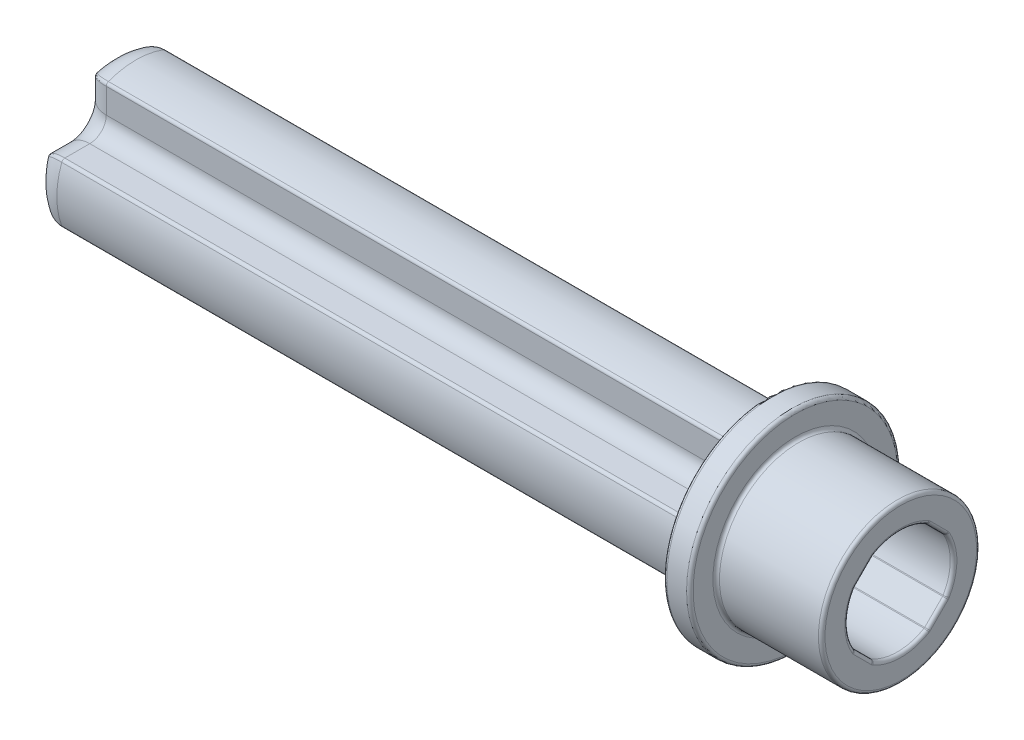
SolidWorks part; units mm, degrees
material "PET"
ref_plane "Alzado" through (0, 0, 0) normal (0, 0, 1) x (1, 0, 0)
ref_plane "Planta" through (0, 0, 0) normal (0, 1, 0) x (1, 0, 0)
ref_plane "Vista lateral" through (0, 0, 0) normal (1, 0, 0) x (0, 0, -1)
sketch "Croquis1" plane through (0, 0, 0) normal (1, 0, 0) x (0, 0, -1)
  line B0 (-1.4, 0.9) -> (-2.2249, 0.9)
  line B1 (0.9, -2.2249) -> (0.9, -1.4)
  line B2 (-0.9, -2.2249) -> (-0.9, -1.4)
  line B3 (2.2249, 0.9) -> (1.4, 0.9)
  line B4 (2.2249, -0.9) -> (1.4, -0.9)
  line B5 (-0.9, 1.4) -> (-0.9, 2.2249)
  line B6 (0.9, 1.4) -> (0.9, 2.2249)
  line B7 (-1.4, -0.9) -> (-2.2249, -0.9)
  arc B8 (-2.2249, 0.9) -> (-2.2249, -0.9) centre (0, 0) ccw
  arc B9 (-1.4, -0.9) -> (-0.9, -1.4) centre (-1.4, -1.4) cw
  arc B10 (0.9, -1.4) -> (1.4, -0.9) centre (1.4, -1.4) cw
  arc B11 (1.4, 0.9) -> (0.9, 1.4) centre (1.4, 1.4) cw
  arc B12 (-0.9, 1.4) -> (-1.4, 0.9) centre (-1.4, 1.4) cw
  arc B13 (0.9, 2.2249) -> (-0.9, 2.2249) centre (0, 0) ccw
  arc B14 (2.2249, -0.9) -> (2.2249, 0.9) centre (0, 0) ccw
  arc B15 (-0.9, -2.2249) -> (0.9, -2.2249) centre (0, 0) ccw
sketch_block_instance "Axle Section Block-1"
sketch_block "Axle Section Block" parameters "D1"=4.8, "D3"=0.5, "D2"=1.8
extrude "Saliente-Extruir1" add sketch "Croquis1" along normal blind 24
sketch "Croquis2" plane through (24, 0, 0) normal (1, 0, 0) x (0, 0, -1)
  circle A0 centre (0, 0) radius 3.2
  dimension "D1" = 6.4
extrude "Saliente-Extruir2" add sketch "Croquis2" against normal blind 4
sketch "Croquis3" plane through (24, 0, 0) normal (1, 0, 0) x (0, 0, -1)
  line L0 (-0.8154, -1.3766) -> (-1.3766, -0.8154)
  line L1 (0.8154, -1.3766) -> (1.3766, -0.8154)
  line L2 (-1.3766, 0.8154) -> (-0.8154, 1.3766)
  line L3 (1.3766, 0.8154) -> (0.8154, 1.3766)
  line L4 (2.192, 0) -> (0, 2.192) construction
  line L5 (2.192, 0) -> (0, -2.192) construction
  line L6 (0, 2.192) -> (-2.192, 0) construction
  line L7 (0, -2.192) -> (-2.192, 0) construction
  line L8 (2.192, 0) -> (-2.192, 0) construction
  line L9 (0, 2.192) -> (0, -2.192) construction
  circle A0 centre (0, 0) radius 2.4
  arc A1 (0.9, 2.2249) -> (-0.9, 2.2249) centre (0, 0) ccw construction
  arc A2 (1.3766, -0.8154) -> (1.3766, 0.8154) centre (0, 0) ccw
  arc A3 (-0.8154, -1.3766) -> (0.8154, -1.3766) centre (0, 0) ccw
  arc A4 (-1.3766, 0.8154) -> (-1.3766, -0.8154) centre (0, 0) ccw
  arc A5 (0.8154, 1.3766) -> (-0.8154, 1.3766) centre (0, 0) ccw
  dimension "D1" = 3.2
  dimension "D2" = 3.1
extrude "Cortar-Extruir1" cut sketch "Croquis3" against normal blind 3.2 flip side to cut
fillet "Redondeo1" radius 0.1 52 edges at (10, -2.2249, -0.9) (10, -0.9, -2.2249) (10, 0.9, -2.2249) (10, 2.2249, -0.9) (10, 2.2249, 0.9) (10, -2.2249, 0.9) (10, -0.9, 2.2249) (10, 0.9, 2.2249) (20.8, 0, -2.4) (20.8, 1.096, 1.096) (22.4, 0.8154, 1.3766) (20.8, 0, 1.6) (22.4, -0.8154, 1.3766) (20.8, -1.096, 1.096) (22.4, -1.3766, 0.8154) (20.8, -1.6, 0) (22.4, -1.3766, -0.8154) (20.8, -1.096, -1.096) (22.4, -0.8154, -1.3766) (20.8, 0, -1.6) (22.4, 0.8154, -1.3766) (20.8, 1.096, -1.096) (22.4, 1.3766, -0.8154) (20.8, 1.6, 0) (22.4, 1.3766, 0.8154) (20, 1.0464, -1.0464) (20, 0.9, -1.8124) (20, 0, -2.4) (20, -0.9, -1.8124) (20, -1.0464, -1.0464) (20, -1.8124, -0.9) (20, -2.4, 0) (20, -1.8124, 0.9) (20, -1.0464, 1.0464) (20, -0.9, 1.8124) (20, 0, 2.4) (20, 0.9, 1.8124) (20, 1.0464, 1.0464) (20, 1.8124, 0.9) (20, 2.4, 0) (20, 1.8124, -0.9) (24, 0, -2.4) (24, 1.096, 1.096) (24, 0, 1.6) (24, -1.096, 1.096) (24, -1.6, 0) (24, -1.096, -1.096) (24, 0, -1.6) (24, 1.096, -1.096) (24, 1.6, 0) (20.8, 0, -3.2) (20, 0, -3.2)
fillet "Redondeo2" radius 0.8 24 edges at (0, 1.7782, 0.9) (0, 1.0464, 1.0464) (0, 0.9, 1.7782) (0, 0, 2.4) (0, -0.9, 1.7782) (0, -1.0464, 1.0464) (0, -1.7782, 0.9) (0, -2.4, 0) (0, -1.7782, -0.9) (0, -1.0464, -1.0464) (0, -0.9, -1.7782) (0, 0, -2.4) (0, 0.9, -1.7782) (0, 1.0464, -1.0464) (0, 1.7782, -0.9) (0, 2.4, 0) (0, -0.8821, -2.2135) (0, 0.8821, -2.2135) (0, 2.2135, -0.8821) (0, 2.2135, 0.8821) (0, 0.8821, 2.2135) (0, -0.8821, 2.2135) (0, -2.2135, 0.8821) (0, -2.2135, -0.8821)
